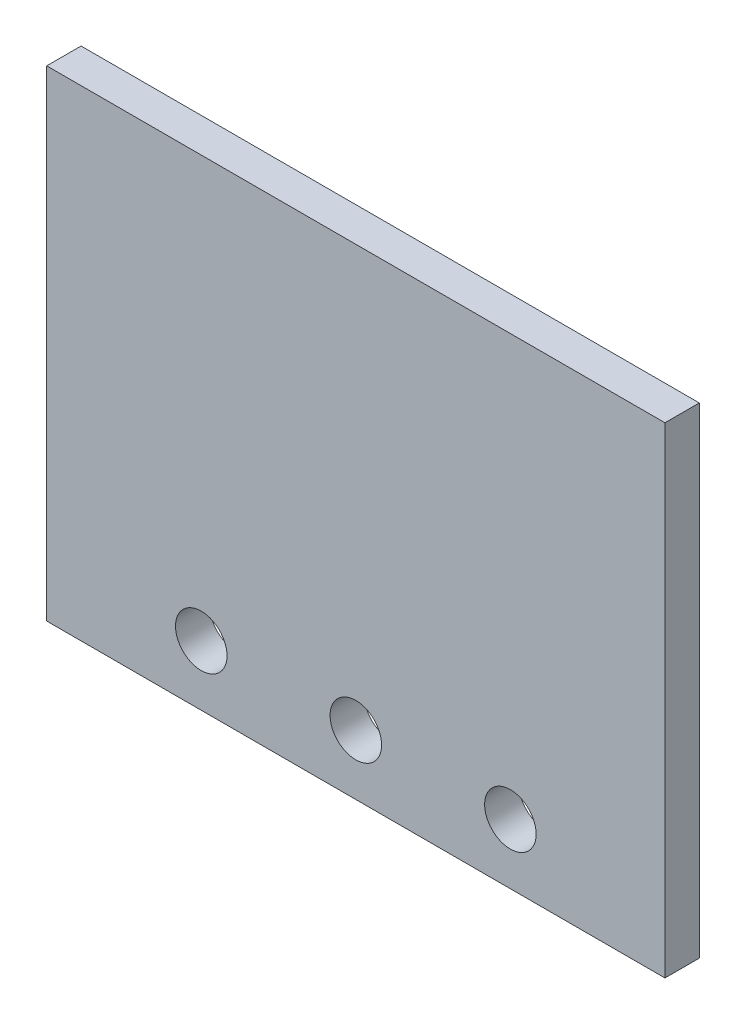
SolidWorks part; units mm, degrees
ref_plane "Piano frontale" through (0, 0, 0) normal (0, 0, 1) x (1, 0, 0)
ref_plane "Piano superiore" through (0, 0, 0) normal (0, 1, 0) x (1, 0, 0)
ref_plane "Piano destro" through (0, 0, 0) normal (1, 0, 0) x (0, 0, -1)
sketch "Schizzo1" plane through (0, 0, 0) normal (0, 0, 1) x (1, 0, 0)
  line L1 (-180, 140) -> (180, 140)
  line L2 (-180, 140) -> (-180, -140)
  line L3 (-180, -140) -> (180, -140)
  line L4 (180, 140) -> (180, -140)
  line L5 (-180, 140) -> (180, -140) construction
  line L6 (-180, -140) -> (180, 140) construction
  circle A0 centre (-90, -105) radius 15
  circle A1 centre (90, -105) radius 15
  circle A2 centre (0, -105) radius 15
  point P0 (0, 0)
  dimension "D3" = 30
  dimension "D4" = 30
  dimension "D5" = 30
  dimension "D1" = 360
  dimension "D2" = 280
extrude "Estrusione-Estrusione1" add sketch "Schizzo1" along normal blind 20
